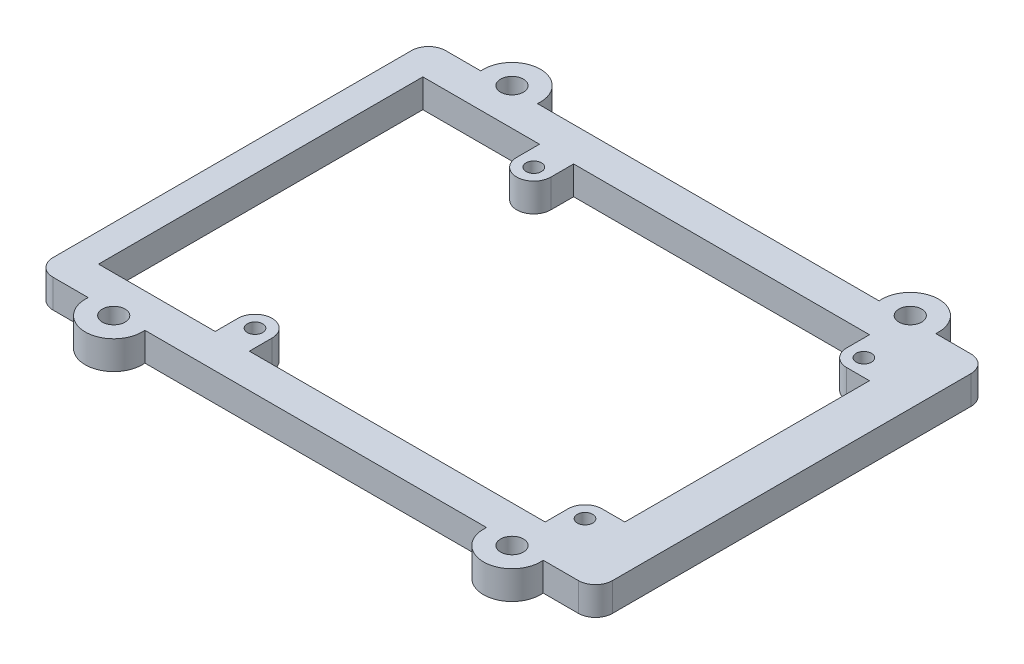
SolidWorks part; units mm, degrees
ref_plane "Plan de face" through (0, 0, 0) normal (0, 0, 1) x (1, 0, 0)
ref_plane "Plan de dessus" through (0, 0, 0) normal (0, 1, 0) x (1, 0, 0)
ref_plane "Plan de droite" through (0, 0, 0) normal (1, 0, 0) x (0, 0, -1)
sketch "Esquisse1" plane through (0, 0, 0) normal (0, 1, 0) x (1, 0, 0)
  line L1 (-29, -24.5) -> (29, -24.5) construction
  line L2 (-29, -24.5) -> (-29, 24.5) construction
  line L3 (-29, 24.5) -> (29, 24.5) construction
  line L4 (29, -24.5) -> (29, 24.5) construction
  line L5 (-29, -24.5) -> (29, 24.5) construction
  line L6 (-29, 24.5) -> (29, -24.5) construction
  line L7 (-40.8367, -34.5) -> (40.8367, -34.5)
  line L8 (-40.8367, -34.5) -> (-40.8367, 34.5) construction
  line L9 (-40.8367, 34.5) -> (40.8367, 34.5)
  line L10 (40.8367, -34.5) -> (40.8367, 34.5)
  line L11 (-40.8367, -34.5) -> (40.8367, 34.5) construction
  line L12 (-40.8367, 34.5) -> (40.8367, -34.5) construction
  line L13 (-40.8367, 34.5) -> (-57.5, 34.5)
  line L14 (-40.8367, 34.5) -> (-40.8367, -34.5) construction
  line L15 (-40.8367, -34.5) -> (-57.5, -34.5)
  line L16 (-57.5, 34.5) -> (-57.5, -34.5)
  circle A0 centre (-29, 24.5) radius 1.35
  circle A1 centre (29, 24.5) radius 1.35
  circle A2 centre (29, -24.5) radius 1.35
  circle A3 centre (-29, -24.5) radius 1.35
  point P0 (0, 0)
  point P10 (0, 0)
  dimension "D3" = 2.7
  dimension "D1" = 58
  dimension "D2" = 49
  dimension "D4" = 10
  dimension "D5" = 86.5
extrude "Boss.-Extru.1" add sketch "Esquisse1" along normal blind 5
sketch "Esquisse2" plane through (0, 5, 0) normal (0, 1, 0) x (1, 0, 0)
  line L0 (-32, 24.5) -> (-32, 28.5)
  line L1 (-57.5, 34.5) -> (-57.5, -34.5) construction
  line L2 (-26, 24.5) -> (-26, 28.5)
  line L3 (26, 24.5) -> (26, 28.5)
  line L4 (29, 21.5) -> (33, 21.5)
  line L6 (-32, -24.5) -> (-32, -28.5)
  line L8 (-26, -24.5) -> (-26, -28.5)
  line L10 (29, -21.5) -> (33, -21.5)
  line L11 (26, -24.5) -> (26, -28.5)
  line L18 (-26, 28.5) -> (26, 28.5)
  line L19 (-52.5, -28.5) -> (-32, -28.5)
  line L20 (-52.5, -28.5) -> (-52.5, 28.5)
  line L21 (-52.5, 28.5) -> (-32, 28.5)
  line L22 (33, -21.5) -> (33, 21.5)
  line L25 (-26, -28.5) -> (26, -28.5)
  circle A0 centre (-29, 24.5) radius 3 construction
  circle A1 centre (29, 24.5) radius 3 construction
  circle A2 centre (29, -24.5) radius 3 construction
  circle A3 centre (-29, -24.5) radius 3 construction
  arc A4 (29, 21.5) -> (26, 24.5) centre (29, 24.5) cw
  arc A5 (-26, 24.5) -> (-32, 24.5) centre (-29, 24.5) cw
  arc A6 (-32, -24.5) -> (-26, -24.5) centre (-29, -24.5) cw
  arc A7 (26, -24.5) -> (29, -21.5) centre (29, -24.5) cw
  point P28 (0, 0)
  point P48 (49.331, 19.7319)
  dimension "D1" = 6
  dimension "D2" = 4
  dimension "D3" = 4
  dimension "D4" = 57
  dimension "D5" = 5
extrude "Enlèv. mat.-Extru.1" cut sketch "Esquisse2" against normal blind 5
sketch "Esquisse3" plane through (0, 5, 0) normal (0, 1, 0) x (1, 0, 0)
  line L0 (40.8367, 34.5) -> (-57.5, 34.5) construction
  line L1 (26.6684, 35) -> (-43.3316, 35) construction
  line L2 (26.6684, 35) -> (26.6684, -35) construction
  line L3 (26.6684, -35) -> (-43.3316, -35) construction
  line L4 (-43.3316, 35) -> (-43.3316, -35) construction
  line L5 (-57.5, 34.5) -> (-57.5, -34.5) construction
  circle A0 centre (-43.3316, 35) radius 2
  circle A1 centre (26.6684, 35) radius 2
  circle A2 centre (26.6684, -35) radius 2
  circle A3 centre (-43.3316, -35) radius 2
  circle A4 centre (-43.3316, 35) radius 5
  circle A5 centre (26.6684, 35) radius 5
  circle A6 centre (26.6684, -35) radius 5
  circle A7 centre (-43.3316, -35) radius 5
  point P6 (-8.3316, 34.5)
  point P7 (-8.3316, -35)
  point P8 (-43.3316, 0)
  point P11 (-57.5, 0)
  dimension "D3" = 4
  dimension "D4" = 10
  dimension "D1" = 70
  dimension "D2" = 70
extrude "Boss.-Extru.2" add sketch "Esquisse3" against normal blind 5
sketch "Esquisse4" plane through (0, 5, 0) normal (0, 1, 0) x (1, 0, 0)
  circle A0 centre (-43.3316, 35) radius 2
  circle A1 centre (26.6684, 35) radius 2
  circle A2 centre (26.6684, -35) radius 2
  circle A3 centre (-43.3316, -35) radius 2
extrude "Enlèv. mat.-Extru.2" cut sketch "Esquisse4" against normal blind 5
fillet "Congé1" radius 3 4 edges at (-57.5, 2.5, 34.5) (-57.5, 2.5, -34.5) (40.8367, 2.5, 34.5) (40.8367, 2.5, -34.5)
